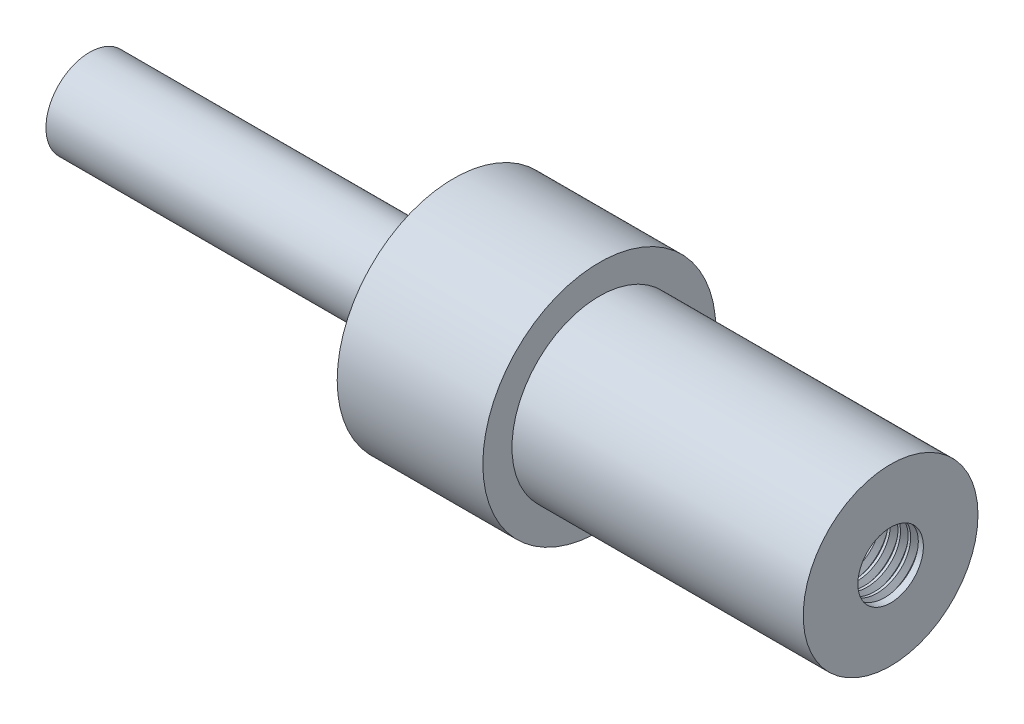
SolidWorks part; units mm, degrees
ref_plane "Front Plane" through (0, 0, 0) normal (0, 0, 1) x (1, 0, 0)
ref_plane "Top Plane" through (0, 0, 0) normal (0, 1, 0) x (1, 0, 0)
ref_plane "Right Plane" through (0, 0, 0) normal (1, 0, 0) x (0, 0, -1)
sketch "Sketch1" plane through (0, 0, 0) normal (0, 0, 1) x (1, 0, 0)
  line L0 (0, 0) -> (0, 3)
  line L1 (0, 3) -> (25, 3)
  line L2 (25, 3) -> (25, 8)
  line L3 (25, 8) -> (35, 8)
  line L4 (35, 8) -> (35, 6)
  line L5 (35, 6) -> (55, 6)
  line L6 (55, 6) -> (55, 0)
  line L7 (55, 0) -> (0, 0)
revolve "Revolve1" add sketch "Sketch1" angle 360 about L7
hole_wizard "M4 Clearance Hole1" positions "Sketch2" profile "Sketch3" hole size "M4" standard "ISO"
sketch "Sketch2" plane through (55, 0, 0) normal (1, 0, 0) x (0, 0, -1)
  point P0 (0, 0)
sketch "Sketch3" plane through (55, 0, 0) normal (0, 1, 0) x (0, 0, -1)
  line L0 (0, 0) -> (0, 11.3519)
  line L1 (0, 11.3519) -> (2.25, 10)
  line L2 (2.25, 10) -> (2.25, 0)
  line L5 (2.25, 0) -> (0, 0)
  line L10 (0, 11.3519) -> (-2.25, 10) construction
  line L11 (0, -6.35) -> (0, 107.95) construction
  dimension "Hole Dia." = 4.5
  dimension "Hole Depth" = 10
  dimension "Drill Angle" = 118
thread "Thread1" pitch 0.7 method cut profile "Thread Profile1" start angle 0, offset 0, length 10, pitch 0.7, diameter 4.5
ref_plane "Plane1" through (55, 0, 2.25) normal (0, -1, 0) x (0, 0, 1)
sketch "Thread Profile1" plane through (55, 0, 2.25) normal (0, -1, 0) x (0, 0, 1)
  line L0 (0, 0) -> (0, 0.7) construction
  line L1 (0, 0) -> (0.3789, 0.2187)
  line L2 (0.3789, 0.2187) -> (0.3789, 0.3062)
  line L3 (0.3789, 0.3062) -> (0, 0.525)
  line L4 (0.3789, 0.2625) -> (0, 0.2625) construction
  line L11 (0, 0) -> (0, 0.525)
  point P2 (0, 0)
  dimension "Pitch" = 0.7
  dimension "Profile_Angle" = 60
  dimension "Profile_Land" = 0.0875
  dimension "Profile_Height" = 0.3789
